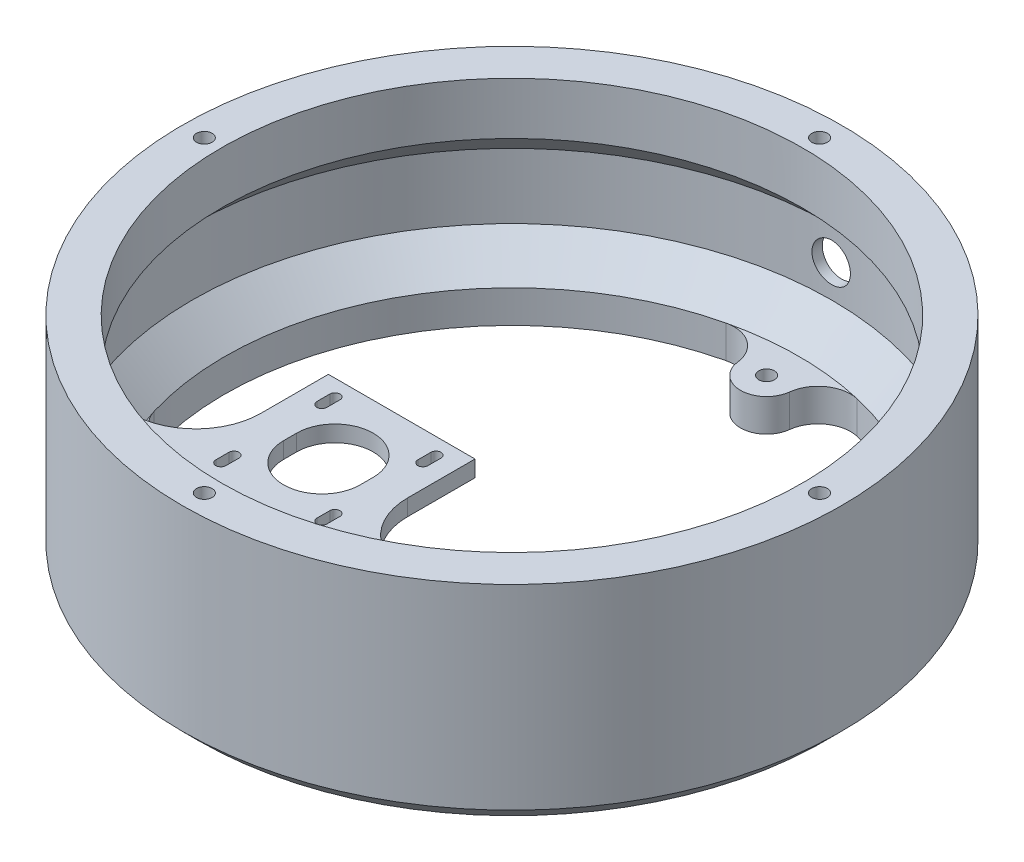
SolidWorks part; units mm, degrees
ref_plane "Front Plane" through (0, 0, 0) normal (0, 0, 1) x (1, 0, 0)
ref_plane "Top Plane" through (0, 0, 0) normal (0, 1, 0) x (1, 0, 0)
ref_plane "Right Plane" through (0, 0, 0) normal (1, 0, 0) x (0, 0, -1)
sketch "Sketch1" plane through (0, 0, 0) normal (0, 1, 0) x (1, 0, 0)
  line L0 (0, -56.33) -> (0, -72.63) construction
  circle A0 centre (0, 0) radius 72.63
  circle A1 centre (0, -56.33) radius 7.5
  circle A2 centre (0, 0) radius 94.415
  circle A3 centre (0, -94.415) radius 2.5
  dimension "D1" = 145.26
  dimension "D3" = 15
  dimension "D4" = 188.83
  dimension "D5" = 5
  dimension "D2" = 16.3
sketch "Sketch3" plane through (0, 0, 0) normal (0, 1, 0) x (-1, 0, 0)
  circle A0 centre (0, 0) radius 101.15
  dimension "D1" = 202.3
sketch "Sketch5" plane through (0, 0, 0) normal (0, -1, 0) x (1, 0, 0)
  line L1 (15.5, 42.83) -> (-15.5, 42.83) construction
  line L2 (15.5, 42.83) -> (15.5, 73.83) construction
  line L3 (15.5, 73.83) -> (-15.5, 73.83) construction
  line L4 (-15.5, 42.83) -> (-15.5, 73.83) construction
  line L5 (15.5, 42.83) -> (-15.5, 73.83) construction
  line L6 (15.5, 73.83) -> (-15.5, 42.83) construction
  line L8 (0, 58.33) -> (0, 54.33) construction
  line L9 (11.75, 58.33) -> (11.75, 54.33)
  line L10 (-11.75, 58.33) -> (-11.75, 54.33)
  line L11 (15.5, 42.83) -> (15.5, 38.83) construction
  line L12 (17.05, 42.83) -> (17.05, 38.83)
  line L13 (13.95, 42.83) -> (13.95, 38.83)
  line L14 (15.5, 73.83) -> (15.5, 69.83) construction
  line L15 (17.05, 73.83) -> (17.05, 69.83)
  line L16 (13.95, 73.83) -> (13.95, 69.83)
  line L17 (-15.5, 73.83) -> (-15.5, 69.83) construction
  line L18 (-13.95, 73.83) -> (-13.95, 69.83)
  line L19 (-17.05, 73.83) -> (-17.05, 69.83)
  line L20 (-15.5, 42.83) -> (-15.5, 38.83) construction
  line L21 (-13.95, 42.83) -> (-13.95, 38.83)
  line L22 (-17.05, 42.83) -> (-17.05, 38.83)
  line L23 (-22.5, 33.83) -> (22.5, 33.83)
  line L24 (-22.5, 33.83) -> (-22.5, 78.83)
  line L25 (-22.5, 78.83) -> (22.5, 78.83)
  line L26 (22.5, 33.83) -> (22.5, 78.83)
  line L27 (-22.5, 33.83) -> (22.5, 78.83) construction
  line L28 (-22.5, 78.83) -> (22.5, 33.83) construction
  arc A0 (11.75, 58.33) -> (-11.75, 58.33) centre (0, 58.33) ccw
  arc A1 (-11.75, 54.33) -> (11.75, 54.33) centre (0, 54.33) ccw
  arc A2 (17.05, 42.83) -> (13.95, 42.83) centre (15.5, 42.83) ccw
  arc A3 (13.95, 38.83) -> (17.05, 38.83) centre (15.5, 38.83) ccw
  arc A4 (17.05, 73.83) -> (13.95, 73.83) centre (15.5, 73.83) ccw
  arc A5 (13.95, 69.83) -> (17.05, 69.83) centre (15.5, 69.83) ccw
  arc A6 (-13.95, 73.83) -> (-17.05, 73.83) centre (-15.5, 73.83) ccw
  arc A7 (-17.05, 69.83) -> (-13.95, 69.83) centre (-15.5, 69.83) ccw
  arc A8 (-13.95, 42.83) -> (-17.05, 42.83) centre (-15.5, 42.83) ccw
  arc A9 (-17.05, 38.83) -> (-13.95, 38.83) centre (-15.5, 38.83) ccw
  point P0 (0, 58.33)
  point P7 (0, 56.33)
  point P9 (0, 56.33)
  point P16 (15.5, 40.83)
  point P22 (15.5, 71.83)
  point P28 (-15.5, 71.83)
  point P34 (-15.5, 40.83)
  dimension "D1" = 3.1
  dimension "D2" = 31
  dimension "D3" = 4
  dimension "D4" = 23.5
  dimension "D5" = 45
  dimension "D6" = 4
  dimension "D7" = 4
  dimension "D8" = 3.1
  dimension "D9" = 45
extrude "Boss-Extrude1" add sketch "Sketch5" along normal blind 5
ref_axis "Axis1" through (0, 0, 56.33) along (0, 1, 0)
sketch "Sketch8" plane through (0, 0, 0) normal (0, 1, 0) x (1, 0, 0)
  circle A0 centre (0, 0) radius 101.15 construction
  circle A1 centre (0, 0) radius 101.15
  circle A2 centre (0, 0) radius 89.15
  circle A4 centre (0, -94.415) radius 2.4
  circle A5 centre (-94.415, 0) radius 2.4
  circle A6 centre (0, 94.415) radius 2.4
  circle A7 centre (94.415, 0) radius 2.4
  point P15 (0, 0)
  dimension "D1" = 4.8
  dimension "D3" = 12
  dimension "D2" = 4
extrude "Boss-Extrude4" add sketch "Sketch8" along normal blind 10 and the other way blind 55 separate body
sketch "Sketch9" plane through (0, -55, 0) normal (0, -1, 0) x (1, 0, 0)
  circle A0 centre (0, 0) radius 98.15
  circle A1 centre (0, 0) radius 101.15 construction
  dimension "D1" = 3
extrude "Cut-Extrude1" cut sketch "Sketch9" against normal up to surface (50 mm away) up to face at (-15.5, -5, 71.83)
sketch "Sketch10" plane through (0, 0, 78.83) normal (0, 0, 1) x (1, 0, 0)
  line L4 (22.5, 0) -> (-22.5, 0)
  line L5 (-22.5, 0) -> (-22.5, -5)
  line L6 (-22.5, -5) -> (22.5, -5)
  line L7 (22.5, -5) -> (22.5, 0)
  line L8 (22.5, 0) -> (-22.5, 0)
  line L9 (-22.5, 0) -> (-22.5, -5)
  line L10 (-22.5, -5) -> (22.5, -5)
  line L11 (22.5, -5) -> (22.5, 0)
  dimension "D1" = 0
extrude "Boss-Extrude5" add sketch "Sketch10" along normal up to next
sketch "Sketch11" plane through (0, -55, 0) normal (0, -1, 0) x (1, 0, 0)
  circle A1 centre (0, 0) radius 101.15
  circle A2 centre (0, 0) radius 101.15
  dimension "D1" = 0
extrude "Boss-Extrude6" add sketch "Sketch11" against normal blind 10
ref_plane "Plane1" through (0, 0, -101.15) normal (0, 0, -1) x (-1, 0, 0)
sketch "Sketch12" plane through (0, 0, -101.15) normal (0, 0, -1) x (-1, 0, 0)
  line L0 (0, -55) -> (0, 10) construction
  line L1 (101.15, 10) -> (-101.15, 10) construction
  line L2 (-101.15, -55) -> (101.15, -55) construction
  circle A0 centre (0, -25) radius 6.985
  dimension "D1" = 13.97
  dimension "D2" = 30
extrude "Boss-Extrude7" add sketch "Sketch12" against normal up to next
sketch "Sketch13" plane through (0, 0, -101.15) normal (0, 0, -1) x (-1, 0, 0)
  circle A0 centre (0, -25) radius 5.9055
  arc A2 (0, -31.985) -> (0, -18.015) centre (0, -25) ccw
  arc A3 (0, -18.015) -> (0, -31.985) centre (0, -25) ccw
  arc A4 (0, -31.985) -> (0, -18.015) centre (0, -25) ccw construction
  arc A5 (0, -18.015) -> (0, -31.985) centre (0, -25) ccw construction
  dimension "D2" = 11.811
  dimension "D1" = 0
extrude "Cut-Extrude2" cut sketch "Sketch13" against normal up to next
fillet "Fillet2" radius 20 2 edges at (-22.5, -2.5, 86.264) (22.5, -2.5, 86.264)
chamfer "Chamfer2" distance 10 angle 45 2 edges at (0, -45, -98.15) (0, -5, 98.15)
chamfer "Chamfer1" distance 5 angle 45 1 edges at (0, -55, 101.15)
sketch "Sketch17" plane through (0, -45, 0) normal (0, 1, 0) x (1, 0, 0)
  line L0 (0, 78.15) -> (0, 88.15) construction
  line L1 (8, 87.7862) -> (8, 78.15)
  line L2 (-8, 78.15) -> (-8, 87.7862)
  arc A1 (8, 87.7862) -> (-8, 87.7862) centre (0, 0) ccw
  circle A2 centre (0, 78.15) radius 2.4
  arc A3 (8, 78.15) -> (-8, 78.15) centre (0, 78.15) cw
  circle A4 centre (0, 0) radius 88.15 construction
  point P2 (7.9163, 87.7786)
  point P9 (0, 0)
  point P10 (-28.4301, 75.7498)
  dimension "D1" = 4.8
  dimension "D3" = 8
  dimension "D2" = 10
sketch "Sketch16" plane through (0, -45, 0) normal (0, 1, 0) x (1, 0, 0)
  circle A1 centre (0, 0) radius 88.15
  circle A5 centre (0, 0) radius 88.15
  dimension "D1" = 0
extrude "Cut-Extrude4" cut sketch "Sketch16" against normal through all
extrude "Boss-Extrude8" add sketch "Sketch17" against normal blind 10
fillet "Fillet4" radius 10 2 edges at (8, -50, -87.7862) (-8, -50, -87.7862)
ref_axis "Axis2" through (0, -55, 0) along (0, 1, 0)
pattern_circular "CirPattern1" count 3 over 360 about axis through (0, -55, 0) along (0, 1, 0) of "Boss-Extrude8", "Fillet4"
